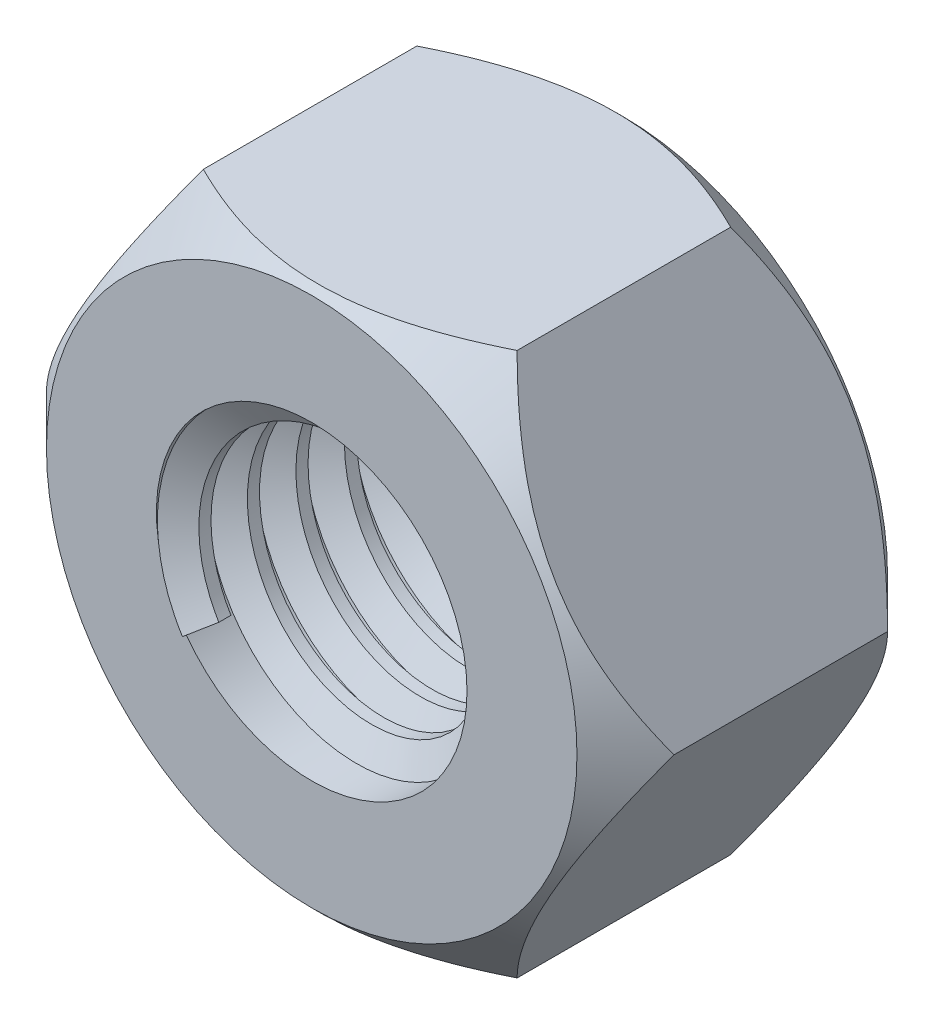
SolidWorks part; units mm, degrees
material "Stainless Steel (ferritic)"
ref_plane "Front Plane" through (0, 0, 0) normal (0, 0, 1) x (1, 0, 0)
ref_plane "Top Plane" through (0, 0, 0) normal (0, 1, 0) x (1, 0, 0)
ref_plane "Right Plane" through (0, 0, 0) normal (1, 0, 0) x (0, 0, -1)
sketch "Sketch1" plane through (0, 0, 0) normal (0, 0, 1) x (1, 0, 0)
  line L0 (0, 11.2125) -> (0, -11.6674) construction
  line L1 (-15.693, 0) -> (14.01, 0) construction
  line L3 (-4.0415, -7) -> (4.0415, -7)
  line L4 (4.0415, -7) -> (8.0829, 0)
  line L5 (8.0829, 0) -> (4.0415, 7)
  line L6 (4.0415, 7) -> (-4.0415, 7)
  line L7 (-4.0415, 7) -> (-8.0829, 0)
  line L8 (-8.0829, 0) -> (-4.0415, -7)
  circle A0 centre (0, 0) radius 7 construction
  dimension "D1" = 14
extrude "Boss-Extrude1" add sketch "Sketch1" along normal mid plane 8
sketch "Sketch2" plane through (0, 0, 4) normal (0, 0, 1) x (1, 0, 0)
  circle A0 centre (0, 0) radius 4
  dimension "D1" = 8
extrude "Cut-Extrude1" [suppressed] cut sketch "Sketch2" against normal blind 8
sketch "Sketch3" plane through (0, 0, 0) normal (0, 1, 0) x (1, 0, 0)
  line L0 (-4.0415, 4) -> (-8.0829, 4) construction
  line L1 (-6.8329, 4) -> (-8.0829, 4)
  line L2 (-8.0829, -4) -> (-8.0829, 4) construction
  line L3 (-8.0829, -4) -> (-8.0829, -2.75)
  line L4 (-4.0415, -4) -> (-8.0829, -4) construction
  line L5 (-6.8329, -4) -> (-8.0829, -4)
  line L6 (-8.0829, 2.75) -> (-6.8329, 4)
  line L7 (-8.0829, -2.75) -> (-6.8329, -4)
  line L8 (-8.0829, 2.75) -> (-8.0829, 4)
  line L9 (0, 5.2748) -> (0, -5.7221) construction
  dimension "D1" = 1.25
  dimension "D2" = 1.25
  dimension "D3" = 1.25
  dimension "D4" = 1.25
revolve "Cut-Revolve1" cut sketch "Sketch3" angle 360 about L9
hole_wizard "Ø8.0mm Dowel Hole2" positions "Sketch4" profile "Sketch5" hole size "Ø8.0" standard "ISO" end condition through all
sketch "Sketch4" plane through (0, 0, -4) normal (0, 0, -1) x (-1, 0, 0)
  point P0 (0, 0)
sketch "Sketch5" plane through (0, 0, -4) normal (1, 0, 0) x (0, 1, 0)
  line L0 (0, 0) -> (0, 8)
  line L1 (0, 8) -> (4, 8)
  line L2 (4, 8) -> (4, 0)
  line L5 (4, 0) -> (0, 0)
  line L11 (0, -6.35) -> (0, 107.95) construction
  dimension "Thru Hole Dia." = 8
  dimension "Thru Hole Depth" = 8
thread "Thread1" pitch 1.25 method extrude profile "Thread Profile3" start angle 0, offset 0, length 7, pitch 1.25, diameter 8
ref_plane "Plane3" through (4, 0, -4) normal (0, -1, 0) x (1, 0, 0)
sketch "Thread Profile3" plane through (4, 0, -4) normal (0, -1, 0) x (1, 0, 0)
  line L0 (0, 0) -> (0, 1.25) construction
  line L11 (0, 0) -> (0, 1.0937)
  line L12 (0, 1.0937) -> (-0.6766, 0.7031)
  line L13 (-0.6766, 0.7031) -> (-0.6766, 0.3906)
  line L15 (-0.6766, 0.3906) -> (0, 0)
  line L17 (-0.6766, 0.5469) -> (0, 0.5469) construction
  point P2 (0, 0)
  dimension "Pitch" = 1.25
  dimension "Profile_Angle" = 60
  dimension "Profile_Land" = 0.3125
  dimension "Profile_Height" = 0.6766
